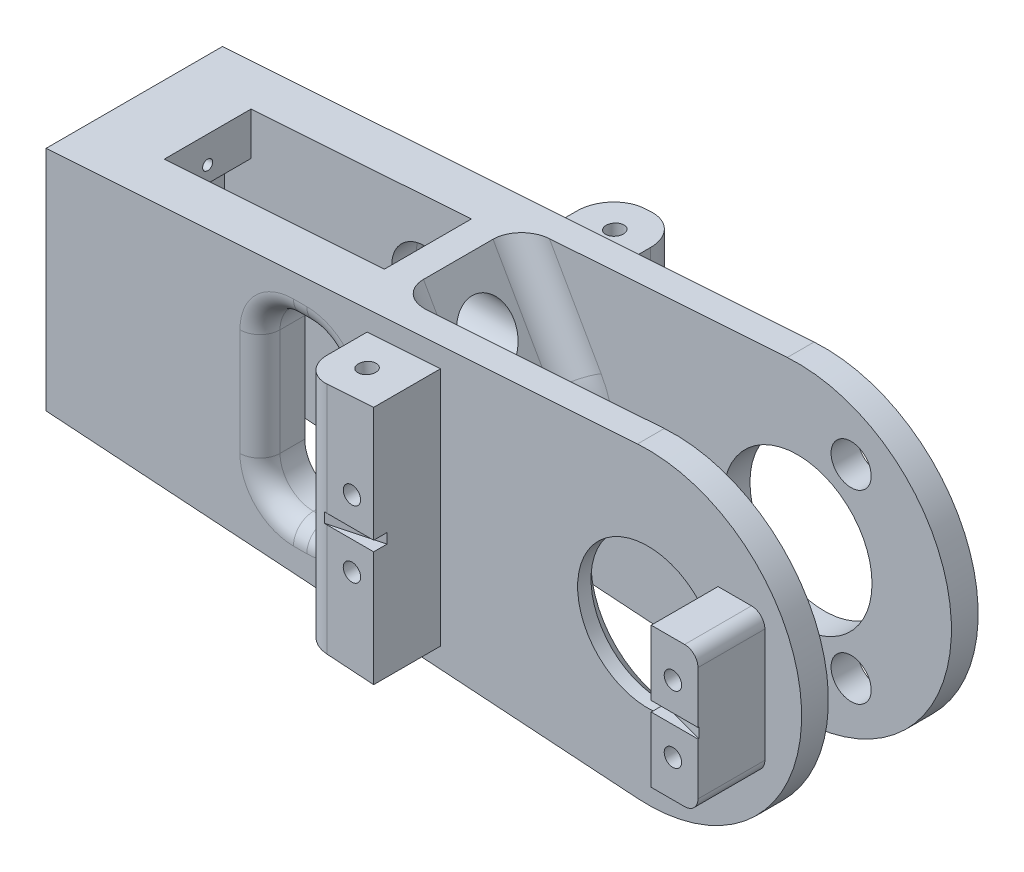
SolidWorks part; units mm, degrees
ref_plane "Front Plane" through (0, 0, 0) normal (0, 0, 1) x (1, 0, 0)
ref_plane "Top Plane" through (0, 0, 0) normal (0, 1, 0) x (1, 0, 0)
ref_plane "Right Plane" through (0, 0, 0) normal (1, 0, 0) x (0, 0, -1)
sketch "Sketch1" plane through (0, 0, 0) normal (0, 0, 1) x (1, 0, 0)
  line L1 (-90, 16.9992) -> (-1.5433, 22.9482)
  line L3 (-90, -17.0004) -> (-1.543, -22.9482)
  line L4 (-90, 16.9992) -> (-90, -17.0004)
  arc A0 (-1.543, -22.9482) -> (-1.5433, 22.9482) centre (0, 0) ccw
extrude "Boss-Extrude2" add sketch "Sketch1" along normal blind 23.2 and the other way blind 13.2
sketch "Sketch5" plane through (0, 0, 0) normal (0, 0, 1) x (1, 0, 0)
  line L0 (-41.55, 20.2576) -> (-1.5433, 22.9482)
  line L1 (-41.55, -20.2582) -> (-1.543, -22.9482)
  line L3 (-90, 16.9992) -> (-90, -17.0004)
  line L4 (-90, -17.0004) -> (-1.543, -22.9482)
  line L5 (-1.5433, 22.9482) -> (-90, 16.9992)
  line L9 (-1.5433, 22.9482) -> (-90, 16.9992) construction
  line L11 (-90, -17.0004) -> (-1.543, -22.9482) construction
  line L14 (-41.55, 20.2576) -> (-32.8532, 4.9367)
  line L15 (-41.55, -20.2582) -> (-32.8531, -4.9366)
  arc A1 (-1.543, -22.9482) -> (-1.5433, 22.9482) centre (0, 0) ccw
  arc A2 (-1.543, -22.9482) -> (-1.5433, 22.9482) centre (0, 0) ccw
  arc A3 (-32.8531, -4.9366) -> (-32.8532, 4.9367) centre (-41.55, 0) ccw
  dimension "D1" = 0
extrude "Cut-Extrude1" cut sketch "Sketch5" against normal mid plane 18.4
sketch "Sketch6" plane through (0, 0, -13.2) normal (0, 0, -1) x (-1, 0, 0)
  circle A0 centre (0, 0) radius 11.125
extrude "Cut-Extrude2" cut sketch "Sketch6" against normal up to next
sketch "Sketch7" plane through (0, 0, 9.2) normal (0, 0, -1) x (-1, 0, 0)
  circle A0 centre (0, 0) radius 10.5
extrude "Cut-Extrude3" cut sketch "Sketch7" against normal up to next
sketch "Sketch8" plane through (0, 0, 23.2) normal (0, 0, 1) x (1, 0, 0)
  line L0 (10.5, -10.5) -> (10.5, 10.5)
  line L1 (10.5, 10.5) -> (-31, 10.5)
  line L2 (-31, -10.5) -> (10.5, -10.5)
  line L3 (-31, 10.5) -> (-31, -10.5)
extrude "Cut-Extrude4" cut sketch "Sketch8" against normal blind 10
sketch "Sketch9" plane through (0, 0, 23.2) normal (0, 0, 1) x (1, 0, 0)
  circle A0 centre (13.75, 5) radius 1.3
  circle A1 centre (-34.25, 5) radius 1.3
  circle A2 centre (13.75, -5) radius 1.3
  circle A3 centre (-34.25, -5) radius 1.3
extrude "Cut-Extrude5" cut sketch "Sketch9" against normal blind 10
sketch "Sketch10" plane through (0, 0, 0) normal (0, 1, 0) x (1, 0, 0)
  line L1 (-31, -23.2) -> (-38.4966, -23.2)
  line L5 (10.5, -23.2) -> (18, -23.2)
  line L6 (10.5, -23.2) -> (10.5, -21.2)
  line L7 (10.5, -21.2) -> (18, -23.2)
  line L8 (-1.5433, -23.2) -> (-90, -23.2) construction
  line L9 (-31, -23.2) -> (-31, -21.2)
  line L10 (-31, -21.2) -> (-38.4966, -23.2)
extrude "Cut-Extrude7" cut sketch "Sketch10" against normal mid plane 1.5
fillet "Fillet1" radius 4 6 edges at (-37.2015, -12.5974, 9.2) (-31.5497, 0.0001, 9.2) (-37.2015, -12.5974, -9.2) (-31.5497, 0.0001, -9.2) (-37.2016, 12.5972, 9.2) (-37.2016, 12.5972, -9.2)
sketch "Sketch11" plane through (0, 0, 0) normal (0, 0, 1) x (1, 0, 0)
  line L0 (-46.0992, 19.9517) -> (-46.0991, -19.9523)
  line L1 (-1.5433, 22.9482) -> (-90, 16.9992) construction
  line L4 (-79.0248, 17.7373) -> (-79.0248, 11.3373)
  line L5 (-79.0248, 11.3373) -> (-83.0248, 11.3373)
  line L6 (-83.0248, 11.3373) -> (-83.0248, -11.6627)
  line L7 (-83.0248, -11.6627) -> (-79.0248, -11.6627)
  line L8 (-79.0248, -11.6627) -> (-79.0248, -17.7384)
  line L9 (-90, -17.0004) -> (-1.543, -22.9482) construction
  line L11 (-79.0248, -17.7384) -> (-46.0991, -19.9523)
  line L12 (-79.0248, 17.7373) -> (-46.0992, 19.9517)
extrude "Cut-Extrude8" cut sketch "Sketch11" against normal mid plane 13
sketch "Sketch12" plane through (-90, 0, 0) normal (-1, 0, 0) x (0, 0, 1)
  arc A0 (2.8925, -0.5794) -> (-2.8925, -0.5794) centre (0, 0) ccw
  arc A2 (-2.8925, -0.5794) -> (2.8925, -0.5794) centre (0, -5.95) ccw
extrude "Cut-Extrude9" cut sketch "Sketch12" against normal up to next
sketch "Sketch13" plane through (-79.0248, 0, 0) normal (1, 0, 0) x (0, 0, -1)
  circle A2 centre (0, -14.05) radius 0.75
  circle A3 centre (0, 13.75) radius 0.75
extrude "Cut-Extrude10" cut sketch "Sketch13" against normal blind 1.5
sketch "Sketch20" plane through (0, 0, 0) normal (1, 0, 0) x (0, 0, -1)
  circle A0 centre (0, 12.5972) radius 4
  circle A1 centre (0, -12.597) radius 4
extrude "Cut-Extrude12" cut sketch "Sketch20" against normal up to next
sketch "Sketch21" plane through (0, 0, 23.2) normal (0, 0, 1) x (1, 0, 0)
  line L0 (-31, -17.9607) -> (-31, 17.9603)
  line L1 (-41.9752, 17.2222) -> (-41.9752, -17.2228)
  line L2 (10.5, 10.5) -> (17.5, 10.5)
  line L3 (-90, 16.9992) -> (-90, -17.0004)
  line L4 (-90, -17.0004) -> (-1.543, -22.9482)
  line L5 (-1.5433, 22.9482) -> (-90, 16.9992)
  line L6 (-90, 16.9992) -> (-90, -17.0004)
  line L7 (-90, -17.0004) -> (-1.543, -22.9482)
  line L8 (-1.5433, 22.9482) -> (-90, 16.9992)
  line L9 (10.5, 10.5) -> (10.5, -10.5)
  line L10 (10.5, -10.5) -> (17.5, -10.5)
  line L11 (17.5, -10.5) -> (17.5, 10.5)
  line L16 (-41.9752, -17.2228) -> (-31, -17.9607)
  line L17 (-31, 17.9603) -> (-41.9752, 17.2222)
  arc A1 (-1.543, -22.9482) -> (-1.5433, 22.9482) centre (0, 0) ccw
  arc A2 (-1.543, -22.9482) -> (-1.5433, 22.9482) centre (0, 0) ccw
  dimension "D1" = 0
extrude "Cut-Extrude13" cut sketch "Sketch21" against normal blind 10
sketch "Sketch22" plane through (0, 0, 13.2) normal (0, 0, 1) x (1, 0, 0)
  line L1 (-58, -13) -> (-46, -13)
  line L2 (-46, -13) -> (-46, 13)
  line L3 (-46, 13) -> (-58, 13)
  line L4 (-58, 13) -> (-58, -13)
extrude "Cut-Extrude14" cut sketch "Sketch22" against normal through all
fillet "Fillet2" radius 5 8 edges at (-58, -13, -9.85) (-58, 13, -9.85) (-58, -13, 9.85) (-46, -13, -8.5898) (-46, -13, 8.5898) (-58, 13, 9.85) (-46, 13, -8.5898) (-46, 13, 8.5898)
fillet "Fillet3" radius 3 16 edges at (-56.5355, 11.5355, -13.2) (-52, 13, -13.2) (-47.4645, 11.5355, -13.2) (-46, 0, -13.2) (-47.4645, -11.5355, -13.2) (-52, -13, -13.2) (-56.5355, -11.5355, -13.2) (-47.4645, -11.5355, 13.2) (-52, -13, 13.2) (-56.5355, -11.5355, 13.2) (-58, 0, 13.2) (-56.5355, 11.5355, 13.2) (-52, 13, 13.2) (-47.4645, 11.5355, 13.2) (-58, 0, -13.2) (-46, 0, 13.2)
sketch "Sketch23" plane through (0, 0, -13.2) normal (0, 0, -1) x (-1, 0, 0)
  line L0 (31, 17.9603) -> (31, 7.9603)
  line L1 (31, 7.9603) -> (41.9752, 7.9603)
  line L2 (31, -17.9607) -> (31, -7.9607)
  line L3 (31, -7.9607) -> (41.9752, -7.9607)
  line L4 (41.9752, 7.9603) -> (41.9752, 17.2222)
  line L8 (31, 17.9603) -> (31, 0.75)
  line L9 (41.9752, 17.2222) -> (31, 17.9603)
  line L10 (41.9752, -17.2228) -> (41.9752, 17.2222)
  line L11 (31, -17.9607) -> (41.9752, -17.2228)
  line L12 (31, -0.75) -> (31, -17.9607)
  line L13 (38.4966, -0.75) -> (31, -0.75)
  line L14 (38.4966, 0.75) -> (38.4966, -0.75)
  line L15 (31, 0.75) -> (38.4966, 0.75)
  line L16 (31, 17.9603) -> (31, 7.9603)
  line L17 (41.9752, 17.2222) -> (31, 17.9603)
  line L18 (41.9752, -17.2228) -> (41.9752, -7.9607)
  line L19 (31, -17.9607) -> (41.9752, -17.2228)
  dimension "D1" = 0
extrude "Boss-Extrude3" add sketch "Sketch23" along normal blind 10 contours L4 L17 L0 L1 | L2 L19 L18 L3
sketch "Sketch24" plane through (-1.342, 19.9549, 0) normal (-0.0671, 0.9977, 0) x (0.9977, 0.0671, 0)
  circle A0 centre (-35.725, -18.2) radius 1.3
extrude "Cut-Extrude15" cut sketch "Sketch24" against normal through all
fillet "Fillet4" radius 4 1 edges at (-41.9752, -0.0003, 23.2)
fillet "Fillet5" radius 2 2 edges at (17.5, -10.5, 18.2) (17.5, 10.5, 18.2)
fillet "Fillet6" radius 5 4 edges at (-31, -12.9607, -23.2) (-41.9752, -12.5918, -23.2) (-41.9752, 12.5913, -23.2) (-31, 12.9603, -23.2)
chamfer "Chamfer1" distance 2 angle 45 1 edges at (-10.5, 0, 9.2)
sketch "Sketch25" plane through (0, 0, -13.2) normal (0, 0, -1) x (-1, 0, 0)
  circle A1 centre (-8, 13.8564) radius 3
  circle A2 centre (-8, -13.8564) radius 3
extrude "Cut-Extrude16" cut sketch "Sketch25" against normal up to next
sketch "Sketch26" plane through (-90, 0, 0) normal (-1, 0, 0) x (0, 0, 1)
  circle A0 centre (0, -5.95) radius 11
extrude "Cut-Extrude17" cut sketch "Sketch26" against normal blind 2
sketch "Sketch28" plane through (0, -7.9607, 0) normal (0, 1, 0) x (1, 0, 0)
  circle A0 centre (-36.3411, 18.2) radius 1.3
extrude "Cut-Extrude18" cut sketch "Sketch28" against normal through all both and the other way through all
